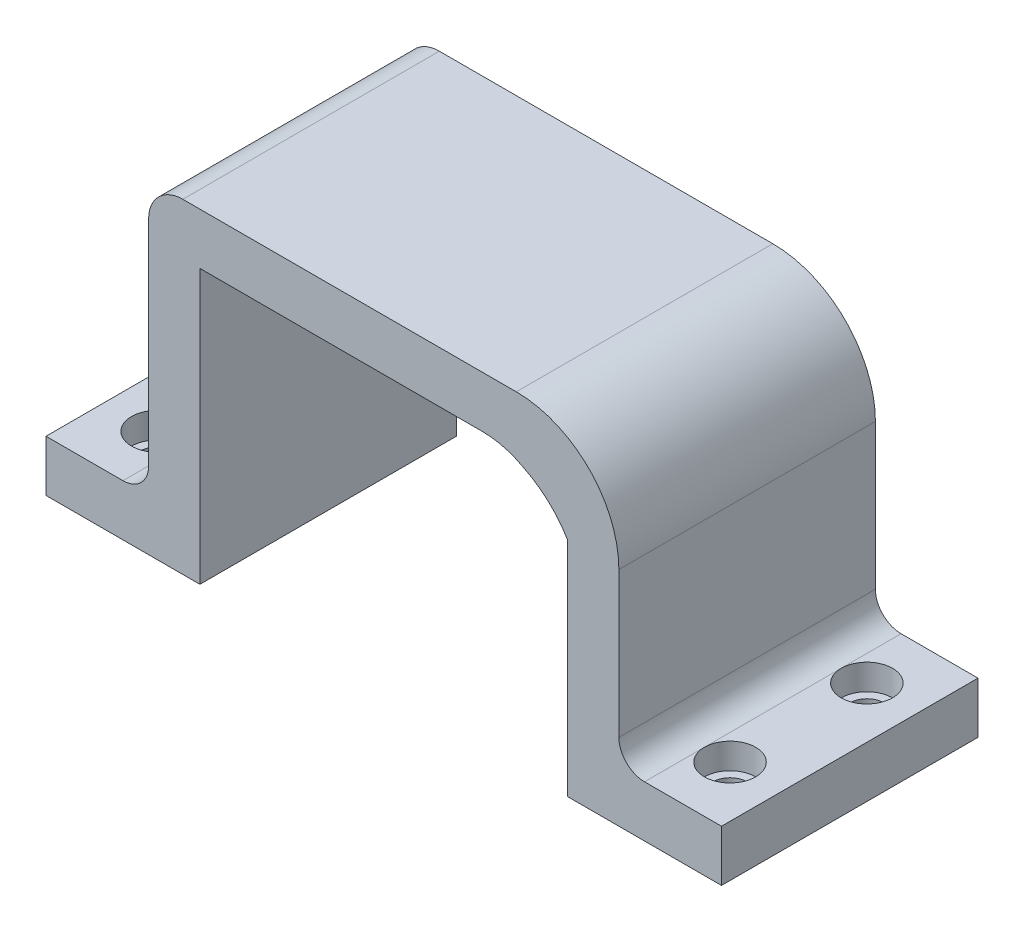
SolidWorks part; units mm, degrees
ref_plane "Front Plane" through (0, 0, 0) normal (0, 0, 1) x (1, 0, 0)
ref_plane "Top Plane" through (0, 0, 0) normal (0, 1, 0) x (1, 0, 0)
ref_plane "Right Plane" through (0, 0, 0) normal (1, 0, 0) x (0, 0, -1)
sketch "Sketch1" plane through (0, 0, 0) normal (0, 0, 1) x (1, 0, 0)
  line L0 (0, 0) -> (18, 0)
  line L1 (18, 0) -> (18, 32)
  line L2 (18, 32) -> (51, 32)
  line L3 (61, 22) -> (61, 0)
  line L4 (61, 0) -> (79, 0)
  line L5 (0, 4) -> (14, 4)
  line L6 (14, 4) -> (14, 36)
  line L7 (14, 36) -> (55, 36)
  line L8 (65, 26) -> (65, 4)
  line L9 (65, 4) -> (79, 4)
  line L10 (0, 0) -> (0, 4)
  line L11 (79, 0) -> (79, 4)
  line L12 (18, 32) -> (61, 32) construction
  line L13 (61, 32) -> (61, 0) construction
  line L14 (65, 36) -> (65, 4) construction
  line L15 (14, 36) -> (65, 36) construction
  arc A0 (51, 32) -> (61, 22) centre (51, 22) cw
  arc A1 (65, 26) -> (55, 36) centre (55, 26) ccw
  point P17 (61, 32)
  dimension "D5" = 10
  dimension "D6" = 10
  dimension "D1" = 32
  dimension "D2" = 43
  dimension "D3" = 18
  dimension "D4" = 4
extrude "Boss-Extrude1" add sketch "Sketch1" along normal blind 30
sketch "Sketch4" plane through (0, 0, 30) normal (0, 0, 1) x (1, 0, 0)
  line L18 (79, 4) -> (65, 4) construction
  line L19 (65, 4) -> (65, 26) construction
  line L20 (55, 36) -> (14, 36) construction
  line L21 (14, 36) -> (14, 4) construction
  line L22 (14, 4) -> (0, 4) construction
  line L23 (79, 6) -> (67, 6)
  line L24 (67, 6) -> (67, 26)
  line L25 (55, 38) -> (12, 38)
  line L26 (12, 38) -> (12, 6)
  line L27 (12, 6) -> (0, 6)
  line L28 (79, 6) -> (67, 6)
  line L29 (67, 6) -> (67, 26)
  line L30 (55, 38) -> (12, 38)
  line L31 (12, 38) -> (12, 6)
  line L32 (12, 6) -> (0, 6)
  line L33 (79, 4) -> (65, 4)
  line L34 (65, 4) -> (65, 26)
  line L35 (55, 36) -> (14, 36)
  line L36 (14, 36) -> (14, 4)
  line L37 (14, 4) -> (0, 4)
  line L38 (0, 6) -> (0, 4)
  line L39 (79, 6) -> (79, 4)
  arc A3 (65, 26) -> (55, 36) centre (55, 26) ccw construction
  arc A4 (67, 26) -> (55, 38) centre (55, 26) ccw
  arc A5 (67, 26) -> (55, 38) centre (55, 26) ccw
  arc A6 (65, 26) -> (55, 36) centre (55, 26) ccw
  dimension "D1" = 2
extrude "Boss-Extrude2" add sketch "Sketch4" against normal up to surface (30 mm away) up to face at (41.7244, 14.5816, 0)
sketch "Sketch2" plane through (0, 4, 0) normal (0, 1, 0) x (1, 0, 0)
  line L3 (0, 0) -> (12, 0) construction
  line L5 (12, -30) -> (0, -30) construction
  line L6 (79, -30) -> (67, -30) construction
  line L7 (67, 0) -> (79, 0) construction
  circle A0 centre (6, -7) radius 2
  circle A1 centre (6, -23) radius 2
  circle A2 centre (73, -7) radius 2
  circle A3 centre (73, -23) radius 2
  circle A4 centre (6, -7) radius 3
  circle A5 centre (6, -23) radius 3
  circle A6 centre (73, -7) radius 3
  circle A7 centre (73, -23) radius 3
  point P4 (6, 0)
  point P13 (73, -30)
  point P22 (0, 0)
  dimension "D2" = 4
  dimension "D4" = 4
  dimension "D7" = 6
  dimension "D1" = 7
  dimension "D3" = 7
  dimension "D5" = 7
  dimension "D6" = 7
extrude "Cut-Extrude1" cut sketch "Sketch2" against normal through all and the other way through all contours A0 | A1 | A3 | A2 region at (6, 4, 7) region at (6, 4, 23) region at (73, 4, 7) region at (73, 4, 23)
extrude "Cut-Extrude3" cut sketch "Sketch2<3>" along normal blind 10 from offset 1 contours A4 A0 | A5 A1 | A7 A3 | A6 A2 region at (3.0849, 4, 7) region at (3.0849, 4, 23) region at (70.0849, 4, 7) region at (70.0849, 4, 23) offset against normal yes
sketch "Sketch2<3>" plane through (0, 4, 0) normal (0, 1, 0) x (1, 0, 0) same geometry as "Sketch2"
sketch "Sketch3" plane through (0, 0, 30) normal (0, 0, 1) x (1, 0, 0)
  line L0 (61, 22) -> (61, 26.0076)
  arc A0 (61, 26.0076) -> (51, 32) centre (50.4101, 19.6754) ccw
  arc A1 (61, 22) -> (51, 32) centre (51, 22) ccw
  arc M5 (51, 32) -> (61, 22) centre (51, 22) cw
extrude "Cut-Extrude2" cut sketch "Sketch3" against normal through all contours L0 A0 M5 region at (59.8623, 26.7528, 30)
fillet "Fillet1" radius 4 1 edges at (12, 38, 15)
fillet "Fillet2" radius 3 2 edges at (67, 6, 15) (12, 6, 15)
